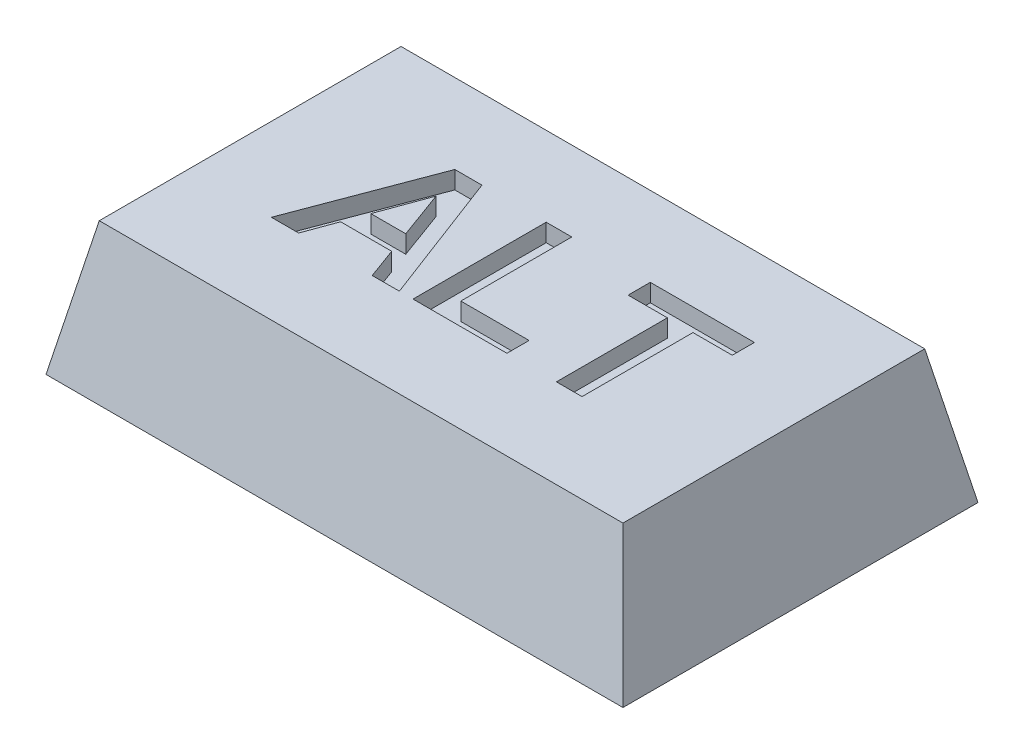
SolidWorks part; units mm, degrees
ref_plane "Front Plane" through (0, 0, 0) normal (0, 0, 1) x (1, 0, 0)
ref_plane "Top Plane" through (0, 0, 0) normal (0, 1, 0) x (1, 0, 0)
ref_plane "Right Plane" through (0, 0, 0) normal (1, 0, 0) x (0, 0, -1)
sketch "Sketch1" plane through (0, 0, 0) normal (0, 1, 0) x (1, 0, 0)
  line L1 (0, 0) -> (13, 0)
  line L2 (0, 0) -> (0, 8)
  line L3 (0, 8) -> (13, 8)
  line L4 (13, 0) -> (13, 8)
  dimension "D1" = 8
  dimension "D2" = 13
extrude "Boss-Extrude1" add sketch "Sketch1" along normal blind 3
sketch "Sketch2" plane through (0, 0, 0) normal (0, 0, 1) x (1, 0, 0)
  line L0 (0, 0) -> (0.6, 3)
  line L1 (0, 3) -> (13, 3) construction
  line L2 (0.6, 3) -> (0, 3)
  line L3 (0, 3) -> (0, 0)
  line L4 (13, 0) -> (12.4, 3)
  line L5 (12.4, 3) -> (13, 3)
  line L6 (13, 3) -> (13, 0)
  dimension "D1" = 0.6
  dimension "D2" = 0.6
extrude "Cut-Extrude1" cut sketch "Sketch2" against normal through all both and the other way through all
sketch "Sketch3" plane through (0, 0, 0) normal (1, 0, 0) x (0, 0, -1)
  line L0 (0, 0) -> (0.6, 3)
  line L1 (8, 3) -> (0, 3) construction
  line L2 (0.6, 3) -> (0, 3)
  line L3 (0, 3) -> (0, 0)
  line L4 (8, 3) -> (7.4, 3)
  line L5 (7.4, 3) -> (8, 0)
  line L6 (8, 3) -> (8, 0)
  dimension "D1" = 0.6
  dimension "D2" = 0.6
extrude "Cut-Extrude2" cut sketch "Sketch3" along normal through all both and the other way through all
sketch "Sketch4" plane through (0, 0, 0) normal (0, -1, 0) x (1, 0, 0)
  line L1 (6.5, 0) -> (6.5, -8) construction
  line L2 (13, -8) -> (0, -8) construction
  line L3 (0, 0) -> (13, 0) construction
  circle A0 centre (6.5, -3.75) radius 1.8
  dimension "D1" = 3.6
  dimension "D2" = 0
  dimension "D3" = 3.75
extrude "Cut-Extrude3" cut sketch "Sketch4" against normal blind 0.8
sketch "Sketch5" plane through (0, 0, 0) normal (0, -1, 0) x (1, 0, 0)
  line L5 (0, 0) -> (13, 0) construction
  line L6 (2.5, -8) -> (10.5, -8)
  line L7 (2.5, -8) -> (2.5, -7)
  line L8 (2.5, -7) -> (10.5, -7)
  line L9 (10.5, -8) -> (10.5, -7)
  point P2 (6.5, 0)
  dimension "D1" = 1
  dimension "D2" = 4
  dimension "D3" = 4
extrude "Boss-Extrude2" add sketch "Sketch5" along normal blind 2
fillet "Fillet1" radius 4 2 edges at (10.5, -2, -7.5) (2.5, -2, -7.5)
sketch "Sketch6" plane through (0, 3, 0) normal (0, 1, 0) x (1, 0, 0)
  text T0 "ALT" font "Arial" height 3
extrude "Cut-Extrude4" cut sketch "Sketch6" against normal blind 0.4
